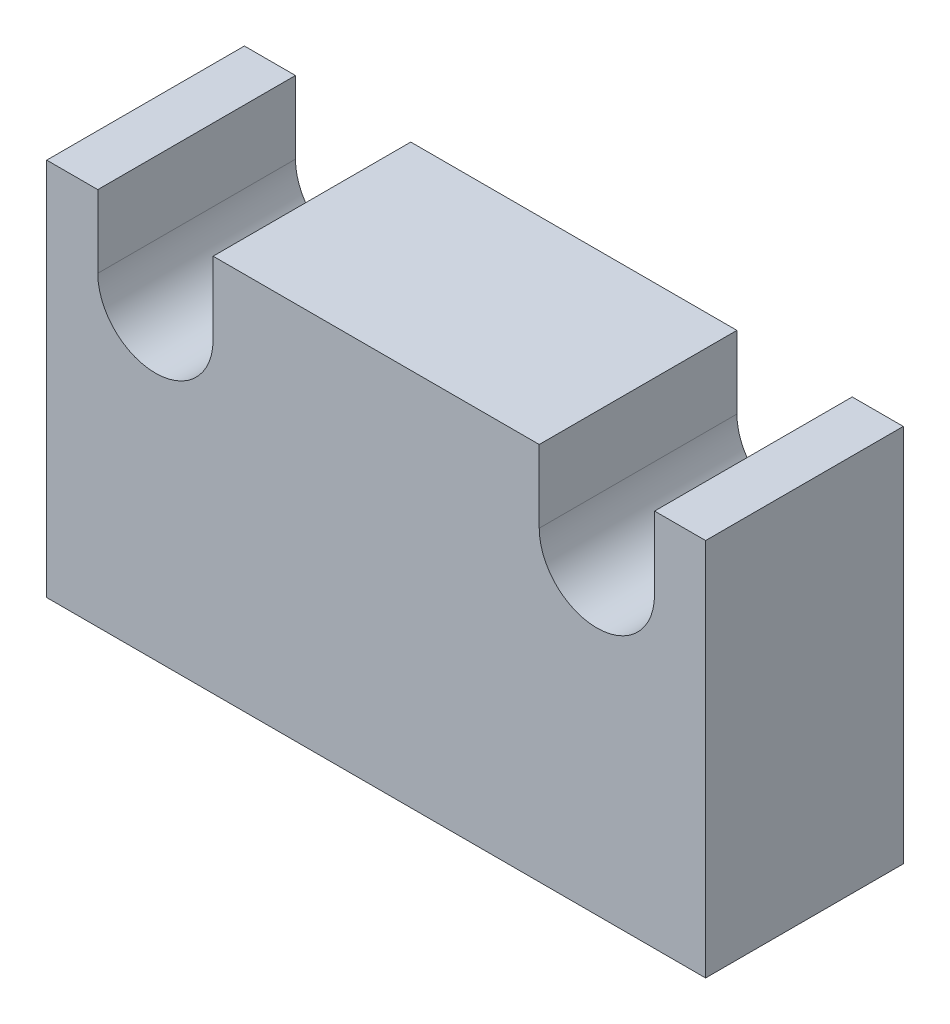
SolidWorks part; units mm, degrees
ref_plane "Front Plane" through (0, 0, 0) normal (0, 0, 1) x (1, 0, 0)
ref_plane "Top Plane" through (0, 0, 0) normal (0, 1, 0) x (1, 0, 0)
ref_plane "Right Plane" through (0, 0, 0) normal (1, 0, 0) x (0, 0, -1)
sketch "Sketch1" plane through (0, 0, 0) normal (0, 1, 0) x (1, 0, 0)
  line L1 (-10, -3) -> (10, -3)
  line L2 (-10, -3) -> (-10, 3)
  line L3 (-10, 3) -> (10, 3)
  line L4 (10, -3) -> (10, 3)
  line L5 (-10, -3) -> (10, 3) construction
  line L6 (-10, 3) -> (10, -3) construction
  point P4 (0, 0)
  point P6 (3.7964, 2.3584)
  point P7 (0, 0)
  dimension "D1" = 20
  dimension "D2" = 6
extrude "Boss-Extrude1" add sketch "Sketch1" along normal blind 11.5
sketch "Sketch2" plane through (0, 0, -3) normal (0, 0, -1) x (-1, 0, 0)
  line L0 (-8.45, 9.3) -> (-8.45, 11.5)
  line L1 (0, 11.5) -> (0, 0) construction
  line L2 (-10, 11.5) -> (10, 11.5) construction
  line L3 (-10, 0) -> (10, 0) construction
  line L4 (-8.45, 11.5) -> (-4.95, 11.5)
  line L5 (-4.95, 11.5) -> (-4.95, 9.3)
  line L6 (4.95, 9.3) -> (4.95, 11.5)
  line L7 (4.95, 11.5) -> (8.45, 11.5)
  line L8 (8.45, 11.5) -> (8.45, 9.3)
  circle A0 centre (-6.7, 9.3) radius 1.75
  circle A1 centre (6.7, 9.3) radius 1.75
  line M4 (10, 11.5) -> (-10, 11.5)
  dimension "D1" = 3.5
extrude "Cut-Extrude1" cut sketch "Sketch2" against normal blind 10 contours A0 L5 L0 M4 | L6 A1 L8 M4 | A1 | A0 M4 region at (-6.7, 11.4587, -3) region at (8.4087, 10.4, -3) region at (6.7, 9.3, -3) region at (-6.7, 9.3, -3)
sketch "Sketch4" plane through (0, 11.5, 0) normal (0, 1, 0) x (1, 0, 0)
  line L1 (-11.3722, -5.8734) -> (11.3722, -5.8734)
  line L2 (-11.3722, -5.8734) -> (-11.3722, 6.7605)
  line L3 (-11.3722, 6.7605) -> (11.3722, 6.7605)
  line L4 (11.3722, -5.8734) -> (11.3722, 6.7605)
  line L5 (-11.3722, -5.8734) -> (11.3722, 6.7605) construction
  line L6 (-11.3722, 6.7605) -> (11.3722, -5.8734) construction
  point P4 (0, 0.4436)
  point P5 (0, 0)
